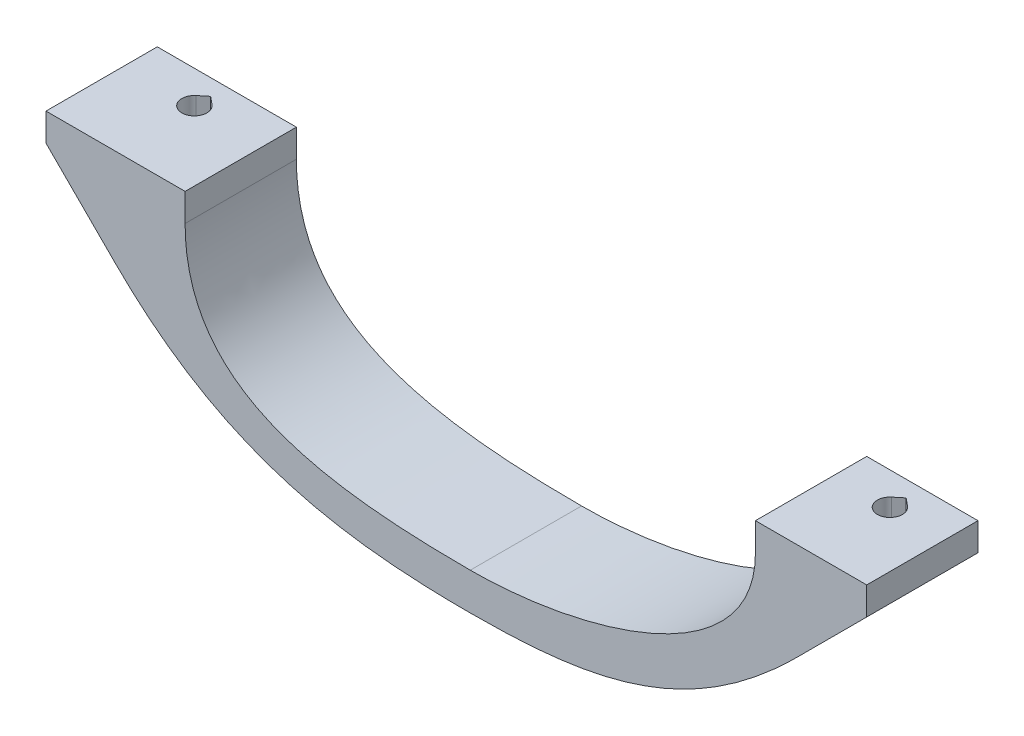
SolidWorks part; units mm, degrees
ref_plane "Front Plane" through (0, 0, 0) normal (0, 0, 1) x (1, 0, 0)
ref_plane "Top Plane" through (0, 0, 0) normal (0, 1, 0) x (1, 0, 0)
ref_plane "Right Plane" through (0, 0, 0) normal (1, 0, 0) x (0, 0, -1)
sketch "Sketch1" plane through (0, 0, 0) normal (0, 0, 1) x (1, 0, 0)
  line L0 (88.5, -40) -> (76.5, -40) construction
  line L1 (15, -40) -> (0, -40) construction
  line L2 (88.5, -40) -> (76.5, -40)
  line L3 (15, -40) -> (0, -40)
  line L4 (15, -40) -> (76.5, -40) construction
  line L5 (45.75, -40) -> (45.75, -60) construction
  line L6 (15, -40) -> (15, -43)
  line L7 (0, -40) -> (0, -43)
  line L8 (63.1923, -60) -> (28.3077, -60) construction
  line L9 (15, -59.2382) -> (15, -24.9064) construction
  line L10 (0, -43) -> (7.5, -50.5)
  line L11 (45.75, -60) -> (45.75, -64) construction
  line L12 (62.5753, -64) -> (28.9247, -64) construction
  line L13 (15.3084, -58.3084) -> (-3.2087, -39.7913) construction
  line L14 (88.5, -40) -> (88.5, -43)
  line L15 (76.5, -40) -> (76.5, -43)
  line L16 (30.6262, -60) -> (60.8738, -60) construction
  line L17 (76.5, -53.9076) -> (76.5, -27.2556) construction
  line L18 (88.5, -43) -> (81, -50.5)
  line L19 (29.8261, -64) -> (61.6739, -64) construction
  line L20 (72.261, -59.239) -> (90.3899, -41.1101) construction
  spline S0 degree 3 poles (15, -43) (15, -57.8895) (29.668, -60) (45.75, -60) knots 0 0 0 0 1 1 1 1
  spline S1 degree 3 poles (7.5, -50.5) (19.0732, -62.0732) (31.7289, -64) (45.75, -64) knots 0 0 0 0 1 1 1 1
  spline S2 degree 3 poles (76.5, -43) (76.5, -54.6616) (58.3532, -60) (45.75, -60) knots 0 0 0 0 1 1 1 1
  spline S3 degree 3 poles (81, -50.5) (69.4421, -62.0579) (59.0199, -64) (45.75, -64) knots 0 0 0 0 1 1 1 1
  dimension "D1" = 20
  dimension "D2" = 3
  dimension "D3" = 7.5
  dimension "D4" = 45
  dimension "D5" = 4
  dimension "D6" = 7.5
  dimension "D7" = 45
extrude "Boss-Extrude1" add sketch "Sketch1" against normal blind 12
sketch "Sketch2" plane through (0, -40, 0) normal (0, 1, 0) x (1, 0, 0)
  line L0 (0, 12) -> (15, 0) construction
  line L1 (76.5, 12) -> (88.5, 0) construction
  line L2 (82.5, 6) -> (82.5, 8.5) construction
  line L5 (7.5, 6) -> (7.5, 8.5) construction
  line L6 (7.5, 12) -> (7.5, 0) construction
  circle A0 centre (7.5, 6) radius 1.35 construction
  circle A1 centre (82.5, 6) radius 1.35 construction
  circle A2 centre (82.5, 8.5) radius 1.35
  circle A3 centre (7.5, 8.5) radius 1.35
  dimension "D1" = 2.7
  dimension "D2" = 2.5
extrude "Cut-Extrude1" cut sketch "Sketch2" against normal through all
ref_plane "Plane1" through (0, -80, 0) normal (0, 1, 0) x (1, 0, 0)
sketch "Sketch4" plane through (0, -80, 0) normal (0, 1, 0) x (1, 0, 0)
  circle A0 centre (7.5, 8.5) radius 2.5
  circle A1 centre (82.5, 8.5) radius 2.5
  circle A2 centre (82.5, 8.5) radius 1.35 construction
  dimension "D1" = 5
extrude "Cut-Extrude3" cut sketch "Sketch4" along normal offset from surface (37 mm away) 3 up to face at (7.5, -40, -7.15)
sketch "Sketch7" plane through (0, -40, 0) normal (0, 1, 0) x (1, 0, 0)
  line L2 (7.5, 9.85) -> (7.5, 10.25) construction
  line L5 (7.5, 10.25) -> (8.359, 9.5414)
  line L6 (7.5, 10.25) -> (6.641, 9.5414)
  arc A2 (8.359, 9.5414) -> (6.641, 9.5414) centre (7.5, 8.5) ccw
  circle A13 centre (7.5, 8.5) radius 1.35 construction
  dimension "D1" = 0.4
extrude "Cut-Extrude4" cut sketch "Sketch7" against normal through all
sketch "Sketch8" plane through (0, -40, 0) normal (0, 1, 0) x (1, 0, 0)
  line L0 (82.5, 9.85) -> (82.5, 10.25) construction
  line L1 (82.5, 10.25) -> (83.359, 9.5414)
  line L2 (82.5, 10.25) -> (81.641, 9.5414)
  circle A0 centre (82.5, 8.5) radius 1.35 construction
  arc A1 (83.359, 9.5414) -> (81.641, 9.5414) centre (82.5, 8.5) ccw
  dimension "D1" = 0.4
extrude "Cut-Extrude5" cut sketch "Sketch8" against normal through all
